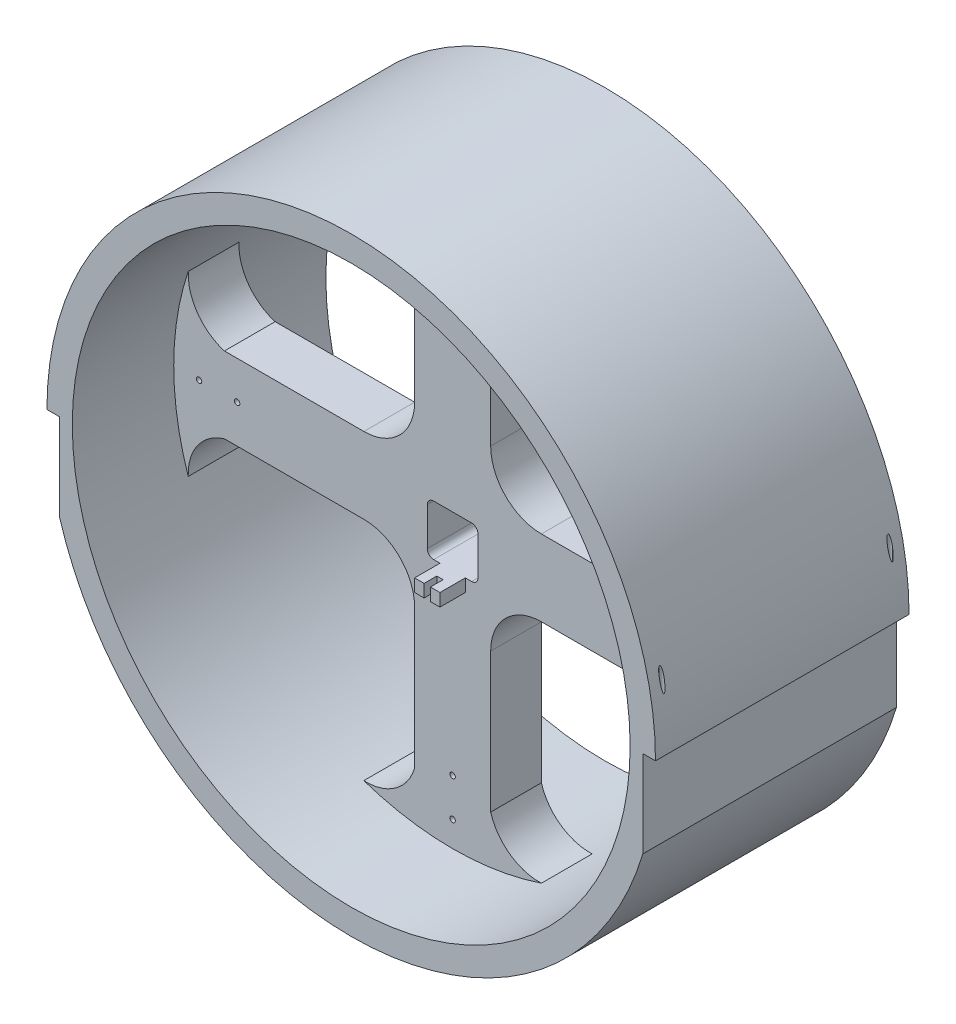
SolidWorks part; units mm, degrees
material "6061 Alloy"
ref_plane "Front Plane" through (0, 0, 0) normal (0, 0, 1) x (1, 0, 0)
ref_plane "Top Plane" through (0, 0, 0) normal (0, 1, 0) x (1, 0, 0)
ref_plane "Right Plane" through (0, 0, 0) normal (1, 0, 0) x (0, 0, -1)
sketch "Sketch1" plane through (0, 0, 0) normal (0, 0, 1) x (1, 0, 0)
  circle A0 centre (0, 0) radius 152.4
  circle A1 centre (0, 0) radius 139.7
  dimension "D1" = 304.8
  dimension "D2" = 279.4
extrude "Boss-Extrude1" add sketch "Sketch1" along normal mid plane 127
sketch "Sketch2" plane through (0, 0, 0) normal (0, 0, 1) x (1, 0, 0)
  line L0 (-114.3, 19.05) -> (-138.7192, 19.05)
  line L1 (-147.1918, -19.05) -> (147.1918, -19.05)
  line L2 (-147.1918, -19.05) -> (-147.1918, 19.05)
  line L3 (-147.1918, 19.05) -> (147.1918, 19.05)
  line L4 (147.1918, -19.05) -> (147.1918, 19.05)
  line L5 (-147.1918, -19.05) -> (147.1918, 19.05) construction
  line L6 (-147.1918, 19.05) -> (147.1918, -19.05) construction
  line L7 (19.05, -143.9568) -> (-19.05, -143.9568)
  line L8 (19.05, -143.9568) -> (19.05, 143.9568)
  line L9 (19.05, 143.9568) -> (-19.05, 143.9568)
  line L10 (-19.05, -143.9568) -> (-19.05, 143.9568)
  line L11 (19.05, -143.9568) -> (-19.05, 143.9568) construction
  line L12 (19.05, 143.9568) -> (-19.05, -143.9568) construction
  line L15 (-44.45, 19.05) -> (-19.05, 19.05)
  line L16 (-19.05, 44.45) -> (-19.05, 19.05)
  line L17 (-132.4254, 44.4927) -> (-143.3503, 19.05)
  line L18 (-143.3503, 19.05) -> (-138.7192, 19.05)
  line L19 (-138.7192, 19.05) -> (-143.3503, 19.05)
  line L20 (-19.05, 114.3) -> (-19.05, 143.9568)
  line L21 (-44.45, 132.4398) -> (-19.05, 143.9568)
  line L22 (44.45, 19.05) -> (19.05, 19.05)
  line L23 (19.05, 44.45) -> (19.05, 19.05)
  line L24 (19.05, 143.3503) -> (19.05, 138.7192)
  line L25 (19.05, 114.3) -> (19.05, 138.7192)
  line L26 (44.4927, 132.4254) -> (19.05, 143.3503)
  line L27 (114.3, 19.05) -> (143.9568, 19.05)
  line L28 (132.4398, 44.45) -> (143.9568, 19.05)
  line L29 (19.05, -44.45) -> (19.05, -19.05)
  line L30 (44.45, -19.05) -> (19.05, -19.05)
  line L31 (143.3503, -19.05) -> (138.7192, -19.05)
  line L32 (114.3, -19.05) -> (138.7192, -19.05)
  line L33 (132.4254, -44.4927) -> (143.3503, -19.05)
  line L34 (19.05, -114.3) -> (19.05, -143.9568)
  line L35 (44.45, -132.4398) -> (19.05, -143.9568)
  line L36 (-44.45, -19.05) -> (-19.05, -19.05)
  line L37 (-19.05, -44.45) -> (-19.05, -19.05)
  line L38 (-19.05, -143.3503) -> (-19.05, -138.7192)
  line L39 (-19.05, -114.3) -> (-19.05, -138.7192)
  line L40 (-44.4927, -132.4254) -> (-19.05, -143.3503)
  line L41 (-114.3, -19.05) -> (-143.9568, -19.05)
  line L42 (-132.4398, -44.45) -> (-143.9568, -19.05)
  arc A1 (-44.45, 19.05) -> (-19.05, 44.45) centre (-44.45, 44.45) ccw
  arc A2 (-114.3, 19.05) -> (-132.4254, 44.4927) centre (-107.0492, 43.3931) cw
  circle A3 centre (0, 0) radius 139.7 construction
  arc A5 (-19.05, 114.3) -> (-44.45, 132.4398) centre (-43.3968, 107.0616) ccw
  arc A6 (19.05, 44.45) -> (44.45, 19.05) centre (44.45, 44.45) ccw
  arc A7 (19.05, 114.3) -> (44.4927, 132.4254) centre (43.3931, 107.0492) cw
  arc A8 (114.3, 19.05) -> (132.4398, 44.45) centre (107.0616, 43.3968) ccw
  arc A9 (44.45, -19.05) -> (19.05, -44.45) centre (44.45, -44.45) ccw
  arc A10 (114.3, -19.05) -> (132.4254, -44.4927) centre (107.0492, -43.3931) cw
  arc A11 (19.05, -114.3) -> (44.45, -132.4398) centre (43.3968, -107.0616) ccw
  arc A12 (-19.05, -44.45) -> (-44.45, -19.05) centre (-44.45, -44.45) ccw
  arc A13 (-19.05, -114.3) -> (-44.4927, -132.4254) centre (-43.3931, -107.0492) cw
  arc A14 (-114.3, -19.05) -> (-132.4398, -44.45) centre (-107.0616, -43.3968) ccw
  point P0 (0, 0)
  point P6 (0, 0)
  point P67 (0, 0)
  dimension "D3" = 25.4
  dimension "D5" = 25.4
  dimension "D1" = 38.1
  dimension "D2" = 38.1
  dimension "D4" = 114.3
  dimension "D6" = 114.3
  dimension "D7" = 4
extrude "Boss-Extrude2" add sketch "Sketch2" along normal mid plane 25.4 contours L1 L10 L3 L2 | L10 L1 L8 L3 | L10 L3 L8 L9 | L8 L1 L4 L3 | L10 L7 L8 L1 | A14 L1 L42 | L10 A13 L40 | A11 L8 L35 | A9 L1 L8 | L1 A10 L33 | A8 L3 L28 | L8 A7 L26 | A5 L10 L21 | L0 A2 L17 L3 | A1 L3 L10 | A6 L8 L3 | A12 L10 L1 region at (-83.1209, 0, 0) region at (-132.2215, 26.1932, 0) region at (-24.7235, 24.7235, 0) region at (0, 81.5034, 0) region at (0, 0, 0) region at (24.7235, 24.7235, 0) region at (83.1209, 0, 0) region at (-24.7235, -24.7235, 0) region at (0, -81.5034, 0) region at (-26.2233, 132.4495, 0) region at (24.7235, -24.7235, 0) region at (-132.4495, -26.2233, 0) region at (132.4495, 26.2233, 0) region at (26.1932, 132.2215, 0) region at (-26.1932, -132.2215, 0) region at (132.2215, -26.1932, 0) region at (26.2233, -132.4495, 0)
sketch "Sketch4" plane through (0, 0, 0) normal (0, 0, 1) x (1, 0, 0)
  line L0 (-12.7, -19.05) -> (-12.7, 6.35)
  line L5 (-12.7, -19.05) -> (12.7, -19.05)
  line L6 (-12.7, 6.35) -> (12.7, 6.35)
  line L7 (12.7, -19.05) -> (12.7, 6.35)
  line L8 (-12.7, -19.05) -> (12.7, 6.35) construction
  line L9 (-12.7, 6.35) -> (12.7, -19.05) construction
  point P1 (0, -6.35)
  dimension "D1" = 25.4
  dimension "D2" = 25.4
  dimension "D3" = 0
  dimension "D4" = 6.35
extrude "Cut-Extrude3" cut sketch "Sketch4" against normal through all both and the other way through all
sketch "Sketch8" plane through (0, 0, 63.5) normal (0, 0, 1) x (1, 0, 0)
  line L0 (-146.05, 0) -> (-163.2527, 0)
  line L1 (-146.05, 0) -> (-146.05, -50.8)
  line L2 (-163.2527, 0) -> (-163.2527, -50.8)
  line L3 (-146.05, -50.8) -> (-163.2527, -50.8)
  circle A0 centre (0, 0) radius 152.4 construction
  dimension "D1" = 50.8
  dimension "D2" = 146.05
extrude "Cut-Extrude5" cut sketch "Sketch8" against normal through all
hole_wizard "#4-40 Tapped Hole2" positions "Sketch21" profile "Sketch22" tap size "#4-40" standard "ANSI Inch" end condition through all
sketch "Sketch21" plane through (0, 0, 0) normal (0, -1, 0) x (-1, 0, 0)
  line L0 (146.05, -63.5) -> (152.4, -63.5) construction
  line L1 (146.05, 63.5) -> (152.4, 63.5) construction
  line L2 (152.4, 63.5) -> (152.4, -63.5) construction
  point P0 (149.225, 57.15)
  point P2 (149.225, -57.15)
  dimension "D1" = 6.35
  dimension "D2" = 6.35
  dimension "D3" = 3.175
  dimension "D4" = 3.175
sketch "Sketch22" plane through (-149.225, 0, -57.15) normal (1, 0, 0) x (0, 0, -1)
  line L0 (0, 0) -> (0, 152.4)
  line L1 (0, 152.4) -> (1.1303, 152.4)
  line L2 (1.1303, 152.4) -> (1.1303, 0)
  line L5 (1.1303, 0) -> (0, 0)
  line L11 (0, -6.35) -> (0, 107.95) construction
  dimension "Thru Tap Drill Dia." = 2.2606
  dimension "Thru Tap Drill Depth" = 152.4
cosmetic thread "Hole Thread7" parameters "D2"=2.8448
cosmetic thread "Hole Thread8" parameters "D2"=2.8448
mirror "Mirror1" about plane through (0, 0, 0) normal (1, 0, 0) of "#4-40 Tapped Hole2", "Cut-Extrude5"
hole_wizard "#4-40 Tapped Hole1" positions "Sketch11" profile "Sketch12" tap size "#4-40" standard "ANSI Inch" end condition through all
sketch "Sketch11" plane through (0, 0, 12.7) normal (0, 0, 1) x (1, 0, 0)
  line L0 (-19.05, 44.45) -> (-19.05, 114.3) construction
  line L1 (44.45, 19.05) -> (114.3, 19.05) construction
  point P0 (-14.2875, 88.9)
  point P2 (-6.0325, 88.9)
  point P4 (88.9, 14.2875)
  point P6 (88.9, 6.0325)
  dimension "D1" = 88.9
  dimension "D2" = 88.9
  dimension "D3" = 8.255
  dimension "D4" = 8.255
  dimension "D5" = 88.9
  dimension "D6" = 4.7625
  dimension "D7" = 4.7625
sketch "Sketch12" plane through (-14.2875, 88.9, 12.7) normal (1, 0, 0) x (0, -1, 0)
  line L0 (0, 0) -> (0, 76.2)
  line L1 (0, 76.2) -> (1.1303, 76.2)
  line L2 (1.1303, 76.2) -> (1.1303, 0)
  line L5 (1.1303, 0) -> (0, 0)
  line L11 (0, -6.35) -> (0, 107.95) construction
  dimension "Thru Tap Drill Dia." = 2.2606
  dimension "Thru Tap Drill Depth" = 76.2
cosmetic thread "Hole Thread1" parameters "D2"=2.8448
cosmetic thread "Hole Thread2" parameters "D2"=2.8448
cosmetic thread "Hole Thread3" parameters "D2"=2.8448
cosmetic thread "Hole Thread4" parameters "D2"=2.8448
hole_wizard "#6-32 Tapped Hole1" positions "Sketch13" profile "Sketch14" tap size "#6-32" standard "ANSI Inch" end condition through all
sketch "Sketch13" plane through (0, 0, 12.7) normal (0, 0, 1) x (1, 0, 0)
  point P0 (-107.95, 0)
  point P2 (-127, 0)
  dimension "D1" = 107.95
  dimension "D2" = 19.05
sketch "Sketch14" plane through (-107.95, 0, 12.7) normal (1, 0, 0) x (0, -1, 0)
  line L0 (0, 0) -> (0, 76.2)
  line L1 (0, 76.2) -> (1.3525, 76.2)
  line L2 (1.3525, 76.2) -> (1.3525, 0)
  line L5 (1.3525, 0) -> (0, 0)
  line L11 (0, -6.35) -> (0, 107.95) construction
  dimension "Thru Tap Drill Dia." = 2.7051
  dimension "Thru Tap Drill Depth" = 76.2
cosmetic thread "Hole Thread5" parameters "D2"=3.5052
cosmetic thread "Hole Thread6" parameters "D2"=3.5052
pattern_circular "CirPattern1" count 4 every 90 about axis through (0, 0, 63.5) along (0, 0, 1) of "#6-32 Tapped Hole1"
sketch "Sketch17" plane through (0, 0, 12.7) normal (0, 0, 1) x (1, 0, 0)
  line L0 (-12.7, -19.05) -> (12.7, -19.05) construction
  line L1 (-12.7, 6.35) -> (-12.7, -19.05) construction
  line L2 (-12.7, -15.875) -> (-12.7, -19.05)
  line L3 (-12.7, -19.05) -> (-9.525, -19.05)
  line L4 (12.7, 6.35) -> (-12.7, 6.35) construction
  line L5 (12.7, -19.05) -> (12.7, 6.35) construction
  line L6 (-12.7, 3.175) -> (-12.7, 6.35)
  line L7 (-12.7, 6.35) -> (-9.525, 6.35)
  line L8 (9.525, 6.35) -> (12.7, 6.35)
  line L9 (12.7, 6.35) -> (12.7, 3.175)
  line L10 (12.7, -15.875) -> (12.7, -19.05)
  line L11 (12.7, -19.05) -> (9.525, -19.05)
  arc A0 (-9.525, -19.05) -> (-12.7, -15.875) centre (-9.525, -15.875) cw
  arc A1 (-12.7, 3.175) -> (-9.525, 6.35) centre (-9.525, 3.175) cw
  arc A2 (9.525, 6.35) -> (12.7, 3.175) centre (9.525, 3.175) cw
  arc A3 (9.525, -19.05) -> (12.7, -15.875) centre (9.525, -15.875) ccw
  dimension "D1" = 3.175
  dimension "D4" = 3.175
  dimension "D5" = 3.175
  dimension "D6" = 3.175
  dimension "D12" = 3.175
  dimension "D2" = 3.175
  dimension "D3" = 3.175
  dimension "D7" = 3.175
  dimension "D8" = 3.175
  dimension "D9" = 3.175
  dimension "D10" = 3.175
  dimension "D11" = 3.175
extrude "Boss-Extrude4" add sketch "Sketch17" against normal up to surface (25.4 mm away) up to face at (1.3525, 107.95, -12.7)
sketch "Sketch18" plane through (0, 0, 12.7) normal (0, 0, 1) x (1, 0, 0)
  line L0 (-9.525, -19.05) -> (9.525, -19.05) construction
  line L1 (-6.35, -19.05) -> (6.35, -19.05)
  line L2 (-6.35, -19.05) -> (-6.35, -25.4)
  line L3 (-6.35, -25.4) -> (6.35, -25.4)
  line L4 (6.35, -19.05) -> (6.35, -25.4)
  line L5 (-12.7, 3.175) -> (-12.7, -15.875) construction
  dimension "D1" = 12.7
  dimension "D2" = 6.35
  dimension "D3" = 6.35
extrude "Boss-Extrude5" add sketch "Sketch18" along normal blind 12.7 and the other way blind 38.1
sketch "Sketch19" plane through (0, -19.05, 0) normal (0, 1, 0) x (1, 0, 0)
  line L0 (6.35, -25.4) -> (-6.35, -25.4) construction
  line L1 (-1.5875, -25.4) -> (1.5875, -25.4)
  line L2 (-1.5875, -25.4) -> (-1.5875, -19.05)
  line L3 (-1.5875, -19.05) -> (1.5875, -19.05)
  line L4 (1.5875, -25.4) -> (1.5875, -19.05)
  line L5 (-6.35, -12.7) -> (-6.35, -25.4) construction
  dimension "D1" = 3.175
  dimension "D2" = 4.7625
  dimension "D3" = 6.35
extrude "Cut-Extrude6" cut sketch "Sketch19" against normal up to next
sketch "Sketch20" plane through (0, -19.05, 0) normal (0, 1, 0) x (1, 0, 0)
  line L0 (6.35, 25.4) -> (-6.35, 25.4) construction
  line L1 (1.5875, 25.4) -> (-1.5875, 25.4)
  line L2 (1.5875, 25.4) -> (1.5875, 19.05)
  line L3 (1.5875, 19.05) -> (-1.5875, 19.05)
  line L4 (-1.5875, 25.4) -> (-1.5875, 19.05)
  line L5 (6.35, 25.4) -> (6.35, 12.7) construction
  dimension "D1" = 3.175
  dimension "D2" = 6.35
  dimension "D3" = 4.7625
extrude "Cut-Extrude7" cut sketch "Sketch20" against normal up to next
